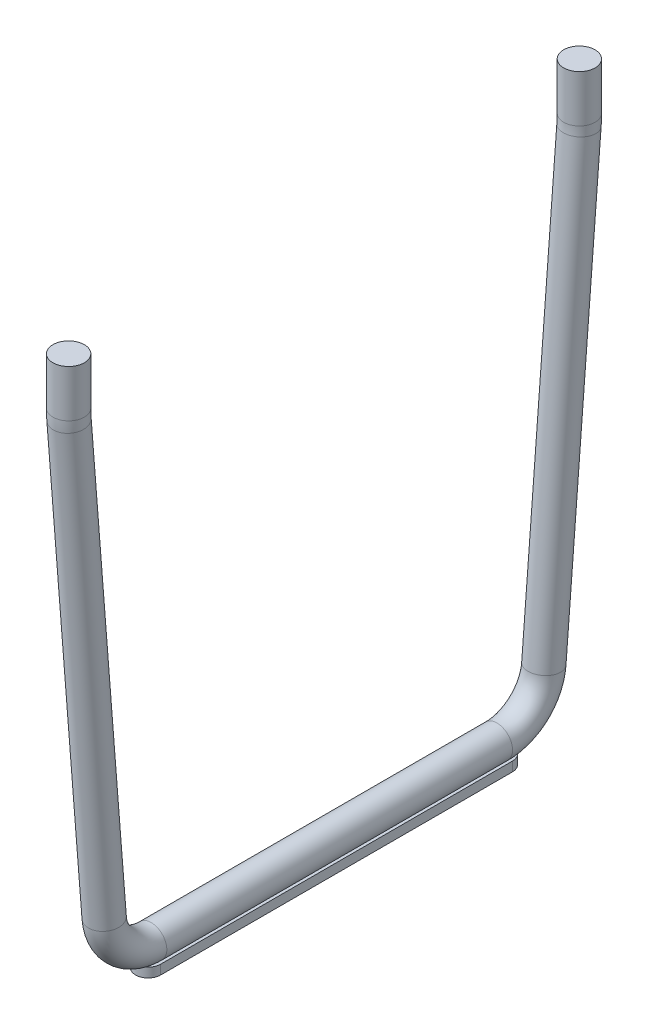
SolidWorks part; units mm, degrees
ref_plane "Front Plane" through (0, 0, 0) normal (0, 0, 1) x (1, 0, 0)
ref_plane "Top Plane" through (0, 0, 0) normal (0, 1, 0) x (1, 0, 0)
ref_plane "Right Plane" through (0, 0, 0) normal (1, 0, 0) x (0, 0, -1)
sketch "Sketch1" plane through (0, 0, 0) normal (0, 1, 0) x (1, 0, 0)
  line L0 (0, 83.2131) -> (0, -85.668) construction
  line L1 (-81.3173, 81.3173) -> (0, 0) construction
  line L2 (0, 0) -> (-96.0833, 0) construction
  circle A0 centre (-81.3173, 81.3173) radius 5
  circle A1 centre (-81.3173, -81.3173) radius 5
  dimension "D2" = 10
  dimension "D1" = 115
  dimension "D3" = 45
ref_plane "Plane1" through (-81.3173, 0, 0) normal (1, 0, 0) x (0, 0, -1)
sketch "Sketch2" plane through (-81.3173, 0, 0) normal (1, 0, 0) x (0, 0, -1)
  line L0 (-81.3173, 0) -> (-81.3173, -15)
  line L1 (-55.0458, -175) -> (55.0458, -175)
  line L2 (-81.1912, -18.2268) -> (-70, -161.1708)
  line L3 (-81.3173, 0) -> (0, 0) construction
  line L4 (81.1912, -18.2268) -> (70, -161.1708)
  line L5 (81.3173, 0) -> (81.3173, -15)
  line L6 (0, 0) -> (0, -175) construction
  arc A0 (-70, -161.1708) -> (-55.0458, -175) centre (-55.0458, -160) ccw
  arc A1 (70, -161.1708) -> (55.0458, -175) centre (55.0458, -160) cw
  arc A2 (-81.3173, -15) -> (-81.1912, -18.2268) centre (-39.975, -15) ccw
  arc A3 (81.3173, -15) -> (81.1912, -18.2268) centre (39.975, -15) cw
  dimension "D4" = 81.3173
  dimension "D3" = 15
  dimension "D1" = 15
  dimension "D2" = 160
  dimension "D5" = 70
sketch "Sketch4" plane through (0, 0, 0) normal (0, 0, 1) x (1, 0, 0)
  line L0 (-81.3173, -175) -> (-81.3173, -161.1708) construction
  line L1 (-81.3173, -175) -> (-81.3173, -161.1708) construction
  circle A0 centre (-81.3173, -175) radius 5
  dimension "D1" = 10
sweep "Sweep7" add profiles "Sketch4" path "Sketch2"
mirror "Mirror2" about plane through (0, 0, 0) normal (0, 0, 1) of "Sweep7"
sketch "Sketch5" plane through (0, 0, 0) normal (0, 0, 1) x (1, 0, 0)
  line L0 (-81.3173, -162.7838) -> (-81.3173, -175) construction
  line L2 (-85.3173, -182) -> (-77.3173, -182)
  line L3 (-85.3173, -182) -> (-85.3173, -179)
  line L4 (-85.3173, -179) -> (-77.3173, -179)
  line L5 (-77.3173, -182) -> (-77.3173, -179)
  line L6 (-85.3173, -182) -> (-77.3173, -179) construction
  line L7 (-85.3173, -179) -> (-77.3173, -182) construction
  circle A1 centre (-81.3173, -175) radius 5
  circle A2 centre (-81.3173, -175) radius 5 construction
  point P1 (-81.3173, -180.5)
  dimension "D2" = 10
  dimension "D3" = 8
  dimension "D4" = 3
  dimension "D5" = 5.5
  dimension "D1" = 0
extrude "Boss-Extrude2" add sketch "Sketch5" along normal blind 56 and the other way blind 56
sketch "Sketch6" plane through (0, 0, 56) normal (0, 0, 1) x (1, 0, 0)
  line L0 (-81.3173, -182) -> (-81.3173, -174.2711) construction
  line L1 (-85.3173, -182) -> (-77.3173, -182) construction
  line L7 (-81.3173, -182) -> (-77.3173, -182)
  line L8 (-81.3173, -182) -> (-81.3173, -179)
  line L9 (-81.3173, -179) -> (-77.3173, -179)
  line L10 (-77.3173, -182) -> (-77.3173, -179)
revolve "Revolve1" add sketch "Sketch6" angle 180 about L0 reverse direction yes
mirror "Mirror3" about plane through (0, 0, 0) normal (0, 0, 1) of "Revolve1"
